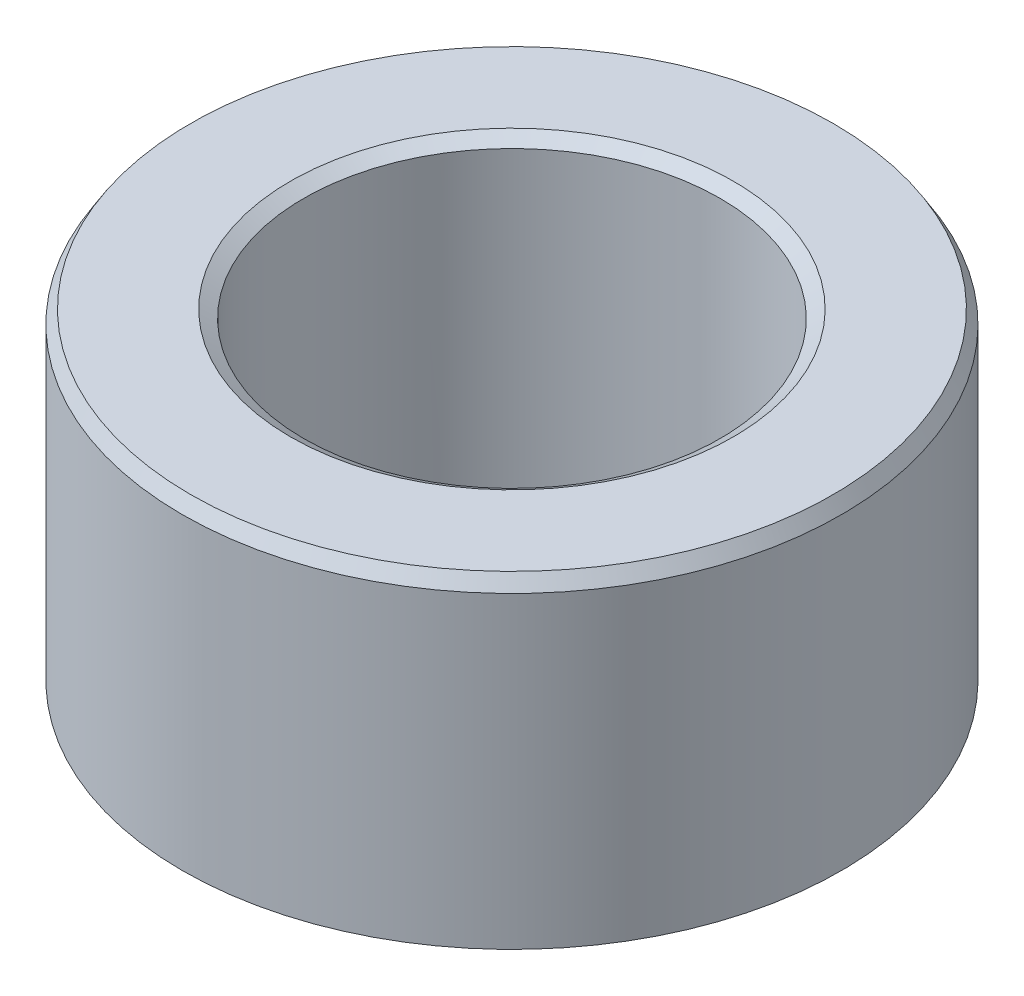
SolidWorks part; units mm, degrees
ref_plane "Front Plane" through (0, 0, 0) normal (0, 0, 1) x (1, 0, 0)
ref_plane "Top Plane" through (0, 0, 0) normal (0, 1, 0) x (1, 0, 0)
ref_plane "Right Plane" through (0, 0, 0) normal (1, 0, 0) x (0, 0, -1)
sketch "Sketch1" plane through (0, 0, 0) normal (0, 1, 0) x (1, 0, 0)
  circle A0 centre (0, 0) radius 45
  dimension "SLEEVE_OD" = 90
extrude "Boss-Extrude1" add sketch "Sketch1" along normal blind 45.029
sketch "Sketch2" plane through (0, 0, 0) normal (0, 1, 0) x (1, 0, 0)
  circle A0 centre (0, 0) radius 28.4235
  dimension "BORE_D" = 56.847
extrude "Cut-Extrude1" cut sketch "Sketch2" along normal through all
chamfer "Chamfer1" distance 1.8202 angle 31.566 4 edges at (0, 45.029, 28.4235) (0, 0, 28.4235) (0, 0, 45) (0, 45.029, 45) first distance on face at (0, 45.029, 28.4235) first distance on face at (0, 0, 28.4235) first distance on face at (0, 45.029, 45)
